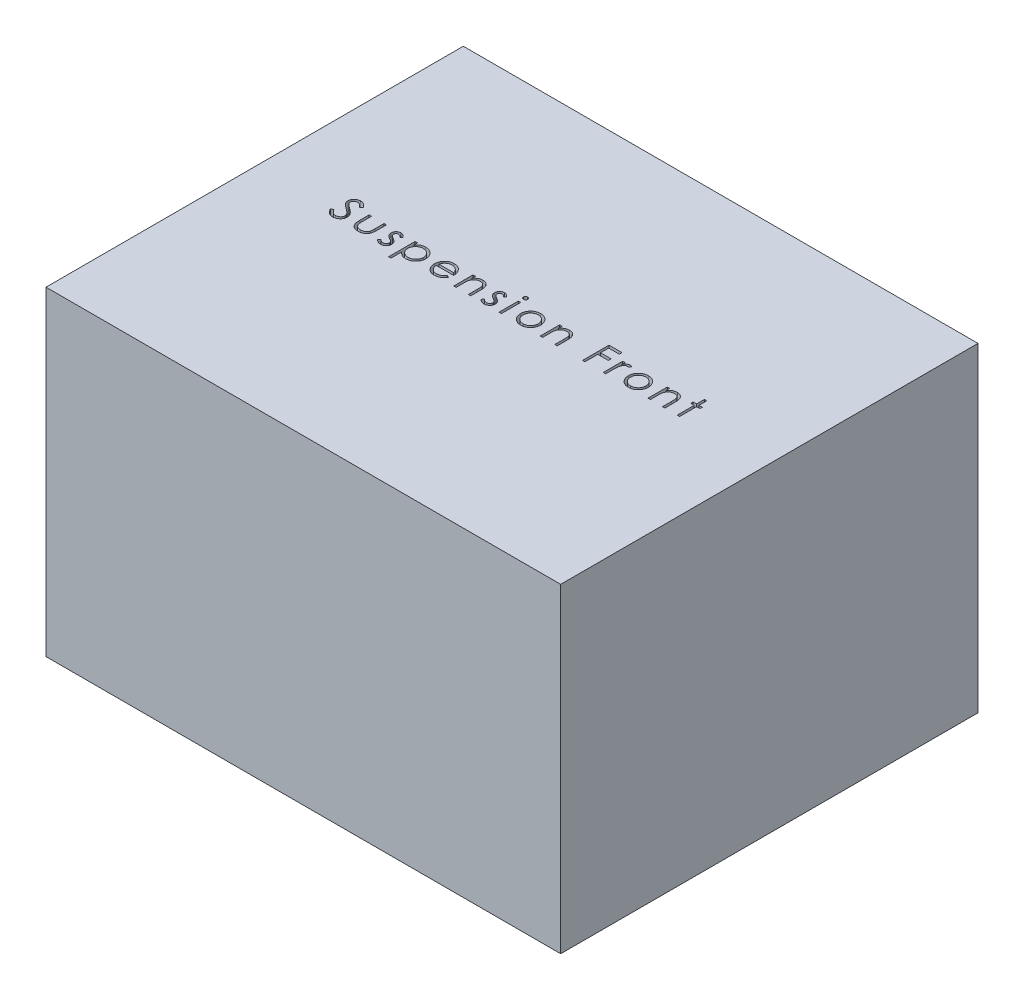
SolidWorks part; units mm, degrees
ref_plane "정면" through (0, 0, 0) normal (0, 0, 1) x (1, 0, 0)
ref_plane "윗면" through (0, 0, 0) normal (0, 1, 0) x (1, 0, 0)
ref_plane "우측면" through (0, 0, 0) normal (1, 0, 0) x (0, 0, -1)
sketch "Sketch1" plane through (0, 0, 0) normal (0, 1, 0) x (1, 0, 0)
  line L1 (185, -150) -> (-185, -150)
  line L2 (185, -150) -> (185, 150)
  line L3 (185, 150) -> (-185, 150)
  line L4 (-185, -150) -> (-185, 150)
  line L5 (185, -150) -> (-185, 150) construction
  line L6 (185, 150) -> (-185, -150) construction
  point P0 (0, 0)
  dimension "D1" = 300
  dimension "D2" = 370
extrude "Boss-Extrude1" add sketch "Sketch1" along normal blind 115 and the other way blind 115
sketch "Sketch2" plane through (0, 115, 0) normal (0, 1, 0) x (1, 0, 0)
  text T0 "Suspension Front" font "Century Gothic" height in points 72
extrude "Cut-Extrude1" cut sketch "Sketch2" against normal blind 30
